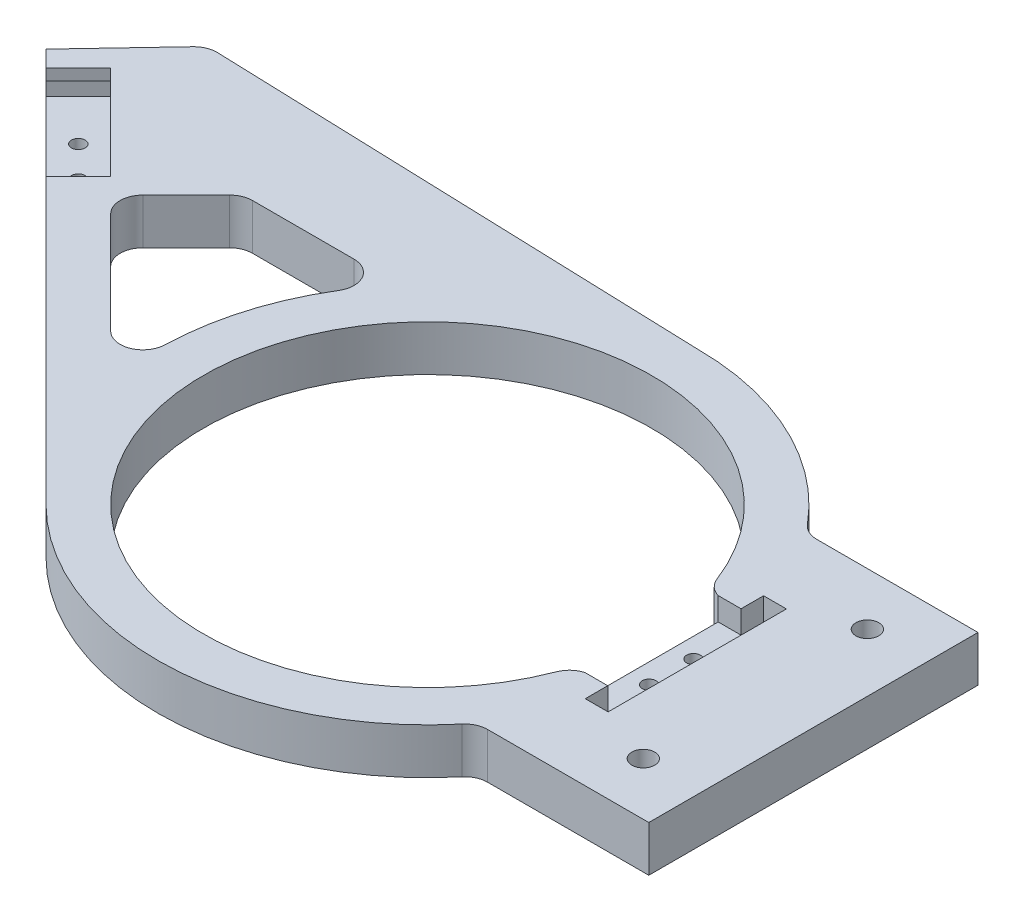
SolidWorks part; units mm, degrees
ref_plane "Front Plane" through (0, 0, 0) normal (0, 0, 1) x (1, 0, 0)
ref_plane "Top Plane" through (0, 0, 0) normal (0, 1, 0) x (1, 0, 0)
ref_plane "Right Plane" through (0, 0, 0) normal (1, 0, 0) x (0, 0, -1)
sketch "Sketch1" plane through (0, 0, 0) normal (0, 1, 0) x (1, 0, 0)
  line L0 (0, 0) -> (58.5, 0) construction
  line L2 (49, 14.5763) -> (46.7817, 14.5763)
  line L3 (49, -14.5763) -> (46.7817, -14.5763)
  line L4 (49, 14.5763) -> (49, -14.5763) construction
  line L5 (-128.004, 44.5654) -> (-107.4626, 24.024) construction
  line L6 (-107.4626, 24.024) -> (-176.0519, -44.5654) construction
  line L7 (-176.0519, -44.5654) -> (-196.5934, -24.024) construction
  line L8 (-196.5934, -24.024) -> (-128.004, 44.5654) construction
  line L9 (-82.0052, -1.4334) -> (-14.7957, -68.6429) construction
  line L10 (-164.6343, -55.983) -> (-127.2203, -93.397) construction
  line L11 (-141.7572, -10.2707) -> (-162.2987, 10.2707) construction
  line L12 (-152.028, 0) -> (0, 0) construction
  line L15 (-107.4626, 24.024) -> (-41.7193, -41.7193)
  line L18 (-93.2961, 23.9997) -> (-57.8861, -11.4103)
  line L19 (-93.2961, 23.9997) -> (-78.8201, 38.4757)
  line L20 (-78.8201, 38.4757) -> (-44.7283, 38.4757)
  line L21 (76.9, 9.5) -> (76.9, -9.5) construction
  line L22 (76.9, 9.5) -> (76.9, 28.5) construction
  line L23 (76.9, -9.5) -> (76.9, -28.5) construction
  line L24 (46.744, 36) -> (84.4, 36)
  line L25 (84.4, 36) -> (84.4, -36)
  line L26 (46.744, -36) -> (84.4, -36)
  line L27 (-110.8386, 62.7409) -> (-128.004, 44.5654)
  line L28 (-128.004, 44.5654) -> (-107.4626, 24.024)
  line L29 (-110.8386, 62.7409) -> (0, 59)
  line L30 (49, 14.5763) -> (49, -14.5763)
  arc A0 (46.7817, 14.5763) -> (46.7817, -14.5763) centre (0, 0) ccw
  arc A1 (46.744, 36) -> (0, 59) centre (0, 0) ccw
  arc A2 (46.7817, 14.5763) -> (46.7817, -14.5763) centre (0, 0) cw construction
  circle A3 centre (76.9, 9.5) radius 2.5 construction
  circle A4 centre (76.9, -9.5) radius 2.5 construction
  circle A5 centre (76.9, 28.5) radius 2.5 construction
  circle A6 centre (76.9, -28.5) radius 2.5 construction
  circle A7 centre (76.9, 19) radius 2.5 construction
  circle A8 centre (76.9, 0) radius 2.5 construction
  circle A9 centre (76.9, -19) radius 2.5 construction
  arc A10 (-44.7283, 38.4757) -> (-57.8861, -11.4103) centre (0, 0) ccw
  arc A11 (-41.7193, -41.7193) -> (46.744, -36) centre (0, 0) ccw
  point P3 (76.9, 28.5)
  point P33 (76.9, 0)
  point P48 (76.9, 19)
  point P49 (76.9, 0)
  point P52 (84.4, 0)
  point P53 (76.9, -19)
  point P54 (76.9, -28.5)
  dimension "D1" = 98
  dimension "D2" = 10
  dimension "D13" = 5
  dimension "D16" = 5
  dimension "D17" = 5
  dimension "D3" = 2.2183
  dimension "D4" = 35.4
  dimension "D5" = 29.05
  dimension "D6" = 97
  dimension "D7" = 45
  dimension "D8" = 25
  dimension "D9" = 34.0918
  dimension "D10" = 1.933
  dimension "D11" = 10
  dimension "D12" = 20.4722
  dimension "D14" = 19
extrude "Boss-Extrude1" add sketch "Sketch1" against normal mid plane 10
fillet "Fillet1" radius 5 9 edges at (46.744, 0, 36) (46.744, 0, -36) (-93.2961, 0, -23.9997) (-78.8201, 0, -38.4757) (-57.8861, 0, 11.4103) (-44.7283, 0, -38.4757) (46.7817, 0, 14.5763) (46.7817, 0, -14.5763) (-110.8386, 0, -62.7409)
sketch "Sketch11" plane through (-41.7193, 0, 41.7193) normal (-0.7071, 0, 0.7071) x (0.7071, 0, 0.7071)
  line L0 (-82.9407, 5) -> (-82.9407, -5) construction
  line L1 (-122.025, -5) -> (0, -5) construction
  line L2 (-82.9407, 5) -> (-82.9407, -5) construction
  line L11 (-119.9635, 0) -> (-122.025, 0) construction
  line L12 (-122.025, -5) -> (-122.025, 5) construction
  line L13 (-85.0022, -0.2756) -> (-82.9407, -0.2756) construction
  line L16 (-116.9635, 5) -> (-116.9635, 2.5)
  line L17 (-122.025, 5) -> (0, 5) construction
  line L18 (-116.9635, 2.5) -> (-119.9635, 2.5)
  line L19 (-119.9635, 2.5) -> (-119.9635, -2.5)
  line L20 (-119.9635, -2.5) -> (-84.9635, -2.5)
  line L21 (-84.9635, -2.5) -> (-84.9635, 2.5)
  line L22 (-84.9635, 2.5) -> (-87.9635, 2.5)
  line L23 (-87.9635, 2.5) -> (-87.9635, 5)
  line L24 (-87.9635, 5) -> (-116.9635, 5)
  dimension "D1" = 35
  dimension "D2" = 5
  dimension "D3" = 3
  dimension "D4" = 2.5
  dimension "D5" = 2.0615
  dimension "D6" = 5.2756
extrude "Cut-Extrude1" cut sketch "Sketch11" against normal blind 10
sketch "Sketch28" plane through (0, -2.5, 0) normal (0, 1, 0) x (1, 0, 0)
  line L0 (-107.1008, 37.8044) -> (-114.1719, 30.7333) construction
  line L1 (-119.4752, 50.1788) -> (-94.7265, 25.43) construction
  line L2 (-126.5463, 43.1077) -> (-101.7975, 18.3589) construction
  line L5 (-113.9951, 37.6276) -> (-107.2776, 30.9101) construction
  line L6 (-113.9951, 37.6276) -> (-117.5307, 34.0921) construction
  line L8 (-107.2776, 30.9101) -> (-110.8132, 27.3746) construction
  point P9 (-110.6364, 34.2688)
  dimension "D1" = 9.5
hole_wizard "Ø3.0mm Dowel Hole3" positions "3DSketch9" profile "Sketch32" hole size "Ø3.0" standard "ANSI Metric" end condition up to next
sketch3d "3DSketch9"
  point P6 (-113.9951, -2.5, -37.6276)
  point P9 (-107.2776, -2.5, -30.9101)
sketch "Sketch32" plane through (-113.9951, -2.5, -37.6276) normal (1, 0, 0) x (0, 0, 1)
  line L0 (0, 0) -> (0, 2.5)
  line L1 (0, 2.5) -> (1.5, 2.5)
  line L2 (1.5, 2.5) -> (1.5, 0)
  line L5 (1.5, 0) -> (0, 0)
  line L11 (0, -6.35) -> (0, 107.95) construction
  dimension "Thru Hole Dia." = 3
  dimension "Thru Hole Depth" = 2.5
sketch "Sketch33" plane through (0, 5, 0) normal (0, 1, 0) x (1, 0, 0)
  line L0 (59, 19.5) -> (59, -19.5)
  line L5 (49, 14.5763) -> (54, 14.5763)
  line L18 (54, 14.5763) -> (54, 19.5)
  line L20 (54, 19.5) -> (59, 19.5)
  line L22 (49, -14.5763) -> (49, 14.5763) construction
  line L23 (49, 14.5763) -> (49, -14.5763)
  line L24 (49, -14.5763) -> (54, -14.5763)
  line L25 (54, -14.5763) -> (54, -19.5)
  line L26 (54, -19.5) -> (59, -19.5)
  dimension "D2" = 39
  dimension "D1" = 5
  dimension "D3" = 10
extrude "Cut-Extrude2" cut sketch "Sketch33" against normal blind 5
sketch "Sketch34" plane through (0, -5, 0) normal (0, -1, 0) x (1, 0, 0)
  line L0 (49, -14.5763) -> (49, -4.8502) construction
  line L1 (49, 14.5763) -> (49, -14.5763) construction
  line L2 (49, -4.8502) -> (53.3276, -4.8502) construction
  line L3 (0, 0) -> (5, 0) construction
  line L4 (49, 4.8502) -> (53.3276, 4.8502) construction
  line L5 (49, 14.5763) -> (49, 4.8502) construction
  dimension "D1" = 5
  dimension "D2" = 9.7261
  dimension "D3" = 4.3276
hole_wizard "Ø3.0mm Press Dowel Hole1" positions "3DSketch10" profile "Sketch35" hole size "Ø3.0" standard "ANSI Metric" end condition up to next
sketch3d "3DSketch10"
  point P0 (53.3276, -5, -4.8502)
  point P3 (53.3276, -5, 4.8502)
sketch "Sketch35" plane through (53.3276, -5, -4.8502) normal (1, 0, 0) x (0, 0, -1)
  line L0 (0, 0) -> (0, 5)
  line L1 (0, 5) -> (1.5, 5)
  line L2 (1.5, 5) -> (1.5, 0)
  line L5 (1.5, 0) -> (0, 0)
  line L11 (0, -6.35) -> (0, 107.95) construction
  dimension "Thru Hole Dia." = 3
  dimension "Thru Hole Depth" = 5
hole_wizard "Ø5.0mm Press Dowel Hole1" positions "3DSketch11" profile "Sketch38" hole size "Ø5.0" standard "ANSI Metric"
sketch3d "3DSketch11"
  line L0 (84.4, 5, -36) -> (59, 5, -36) construction
  line L1 (84.4, 5, -36) -> (49.1426, 5, -36) construction
  line L3 (49.1426, 5, 36) -> (84.4, 5, 36) construction
  line L4 (59, 5, 36) -> (84.4, 5, 36) construction
  line L5 (84.4, 5, 36) -> (84.4, 5, -36) construction
  line L8 (59, 5, -36) -> (59, 5, 36) construction
  line L10 (59, 5, 19.5) -> (59, 5, -19.5) construction
  line L11 (84.4, 5, 0) -> (59, 5, 0) construction
  line L13 (71.7, 5, 24.5) -> (71.7, 5, -24.5) construction
  point P0 (71.7, 5, 24.5)
  point P2 (71.7, 5, -24.5)
  point P77 (71.7, 5, 0)
  dimension "D1" = 49
sketch "Sketch38" plane through (71.7, 5, 24.5) normal (1, 0, 0) x (0, 0, 1)
  line L0 (0, 0) -> (0, 10)
  line L1 (0, 10) -> (2.5, 10)
  line L2 (2.5, 10) -> (2.5, 0)
  line L5 (2.5, 0) -> (0, 0)
  line L11 (0, -6.35) -> (0, 107.95) construction
  dimension "Thru Hole Dia." = 5
  dimension "Thru Hole Depth" = 10
